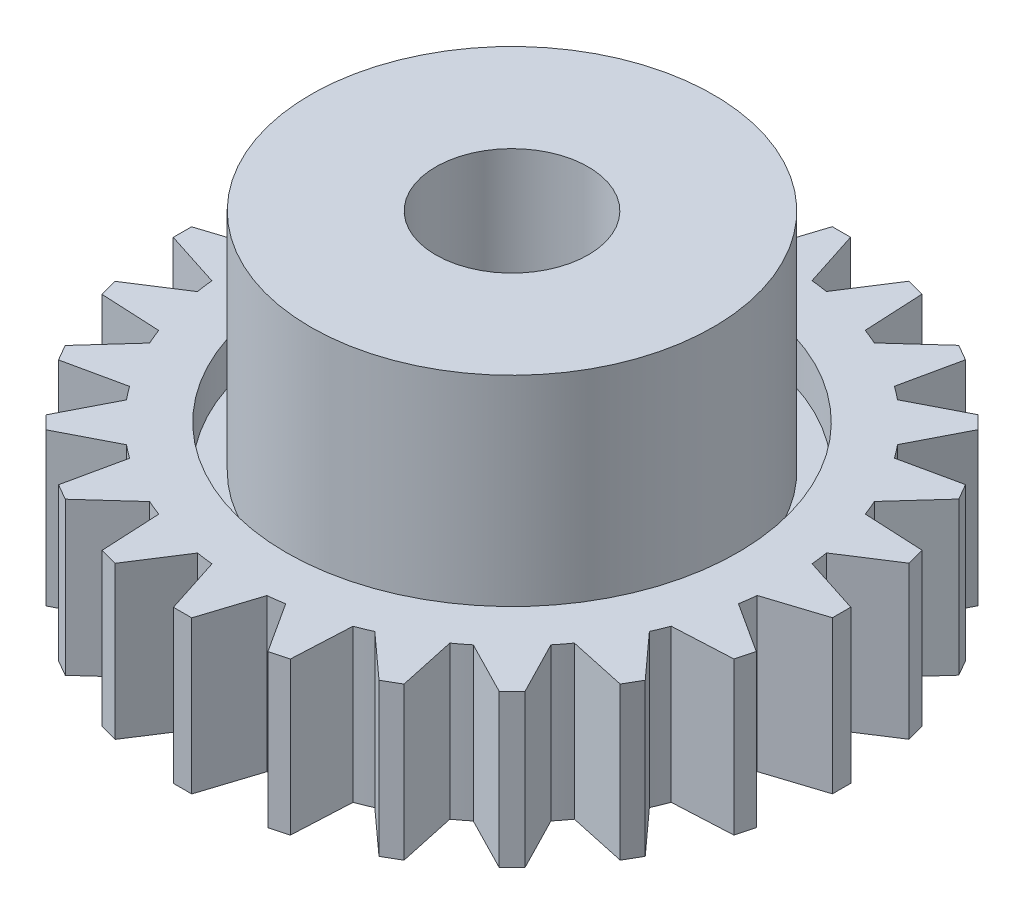
SolidWorks part; units mm, degrees
ref_plane "Front Plane" through (0, 0, 0) normal (0, 0, 1) x (1, 0, 0)
ref_plane "Top Plane" through (0, 0, 0) normal (0, 1, 0) x (1, 0, 0)
ref_plane "Right Plane" through (0, 0, 0) normal (1, 0, 0) x (0, 0, -1)
sketch "Sketch1" plane through (0, 0, 0) normal (0, 1, 0) x (1, 0, 0)
  circle A0 centre (0, 0) radius 13.716 construction
  circle A1 centre (0, 0) radius 11.4046
  circle A2 centre (0, 0) radius 3.175
  circle A3 centre (0, 0) radius 8.382
  circle A4 centre (0, 0) radius 9.398
  dimension "D1" = 27.432
  dimension "D2" = 22.8092
  dimension "D3" = 6.35
  dimension "D4" = 16.764
  dimension "D5" = 18.796
extrude "Boss-Extrude1" add sketch "Sketch1" along normal blind 6.35 contours A0 A1 | A1 A3 | A4 A3 region at (-11.082, 0, 0) region at (-9.1322, 0, 0)
extrude "Boss-Extrude2" add sketch "Sketch1<3>" along normal blind 13.97 contours A3 A2 region at (-8.1449, 0, 0)
sketch "Sketch1<3>" plane through (0, 0, 0) normal (0, 1, 0) x (1, 0, 0) same geometry as "Sketch1"
extrude "Cut-Extrude1" cut sketch "Sketch1<4>" along normal blind 1.778 contours A4 A3 region at (-9.1322, 0, 0)
sketch "Sketch1<4>" plane through (0, 0, 0) normal (0, 1, 0) x (1, 0, 0) same geometry as "Sketch1"
extrude "Cut-Extrude3" cut sketch "Sketch1<8>" against normal blind 1.778 from offset 6.35 contours A4 A3 region at (-9.1322, 0, 0)
sketch "Sketch1<8>" plane through (0, 0, 0) normal (0, 1, 0) x (1, 0, 0) same geometry as "Sketch1"
sketch "Sketch2" plane through (0, 6.35, 0) normal (0, 1, 0) x (1, 0, 0)
  line L1 (-0.3847, 13.716) -> (0.3773, 13.716)
  line L2 (-13.203, -25.5169) -> (-7.633, -8.4736)
  line L3 (0.3773, 13.716) -> (1.1401, 11.3475)
  line L4 (-1.1459, 11.3469) -> (-0.3847, 13.716)
  line L5 (7.4545, -8.631) -> (12.6586, -25.0719)
  circle A1 centre (0, 0) radius 31.75 construction
  circle A2 centre (0, 0) radius 13.716 construction
  circle A3 centre (0, 0) radius 11.4046
  point P10 (-0.0037, 13.716)
  point P12 (1.1556, 11.3459)
  circle M11 centre (0, 0) radius 11.4046
  dimension "D1" = 22.8092
  dimension "D3" = 63.5
  dimension "D5" = 27.432
  dimension "D2" = 2.286
  dimension "D4" = 0.762
extrude "Boss-Extrude3" add sketch "Sketch2" against normal blind 6.35 contours L3 L1 L2 M11 | A3 L3 L2 M11 region at (-0.0032, 6.35, -12.3581)
pattern_circular "CirPattern1" count 24 over 360 about axis through (0, 6.35, 0) along (0, -1, 0) of "Boss-Extrude3"
